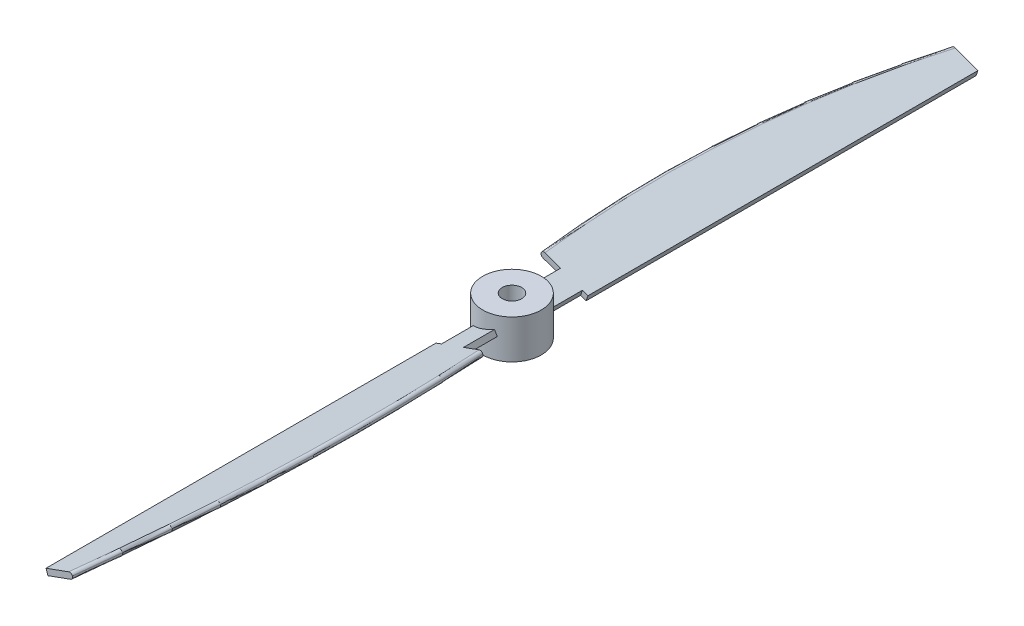
SolidWorks part; units mm, degrees
material "PBT General Purpose"
ref_plane "Front Plane" through (0, 0, 0) normal (0, 0, 1) x (1, 0, 0)
ref_plane "Top Plane" through (0, 0, 0) normal (0, 1, 0) x (1, 0, 0)
ref_plane "Right Plane" through (0, 0, 0) normal (1, 0, 0) x (0, 0, -1)
sketch "Sketch1" plane through (0, 0, 0) normal (0, 1, 0) x (1, 0, 0)
  circle A0 centre (0, 0) radius 5
  circle A1 centre (0, 0) radius 15
  dimension "D1" = 30
  dimension "D2" = 10
extrude "Boss-Extrude1" add sketch "Sketch1" along normal mid plane 20
sketch "Sketch2" plane through (0, 0, 0) normal (0, 0, 1) x (1, 0, 0)
  line L0 (0, 0) -> (-15.207, 5.5349) construction
  line L3 (0, 0) -> (0, 15.6947) construction
  dimension "D1" = 70
ref_plane "Plane1" through (0, 0, 0) normal (0.342, 0.9397, 0) x (-0.9397, 0.342, 0)
sketch "Sketch3" plane through (0, 0, 0) normal (0.342, 0.9397, 0) x (-0.9397, 0.342, 0)
  line L1 (6, -13) -> (6, -30)
  line L2 (6, -30) -> (16, -30)
  line L4 (4.9131, -230) -> (-9, -230)
  line L5 (-9, -230) -> (-9, -30)
  line L6 (-9, -30) -> (-6, -30)
  line L7 (-6, -30) -> (-6, -13)
  arc A0 (16, -30) -> (4.9131, -230) centre (-651, -93.3325) cw
  arc A1 (-6, -13) -> (6, -13) centre (0, 2.906) ccw
  point P26 (0, -14.094)
  dimension "D1" = 17
  dimension "D5" = 670
  dimension "D8" = 28
  dimension "D2" = 12
  dimension "D3" = 3
  dimension "D4" = 25
  dimension "D6" = 200
  dimension "D7" = 17
  dimension "D9" = 30
extrude "Boss-Extrude2" add sketch "Sketch3" along normal mid plane 3
fillet "Fillet1" radius 1.5 2 edges at (-16.376, 7.5566, -130.4167) (-17.402, 4.7376, -130.4167)
pattern_circular "CirPattern1" count 2 over 360 about axis through (0, 10, 0) along (0, -1, 0) of "Boss-Extrude2", "Fillet1"
